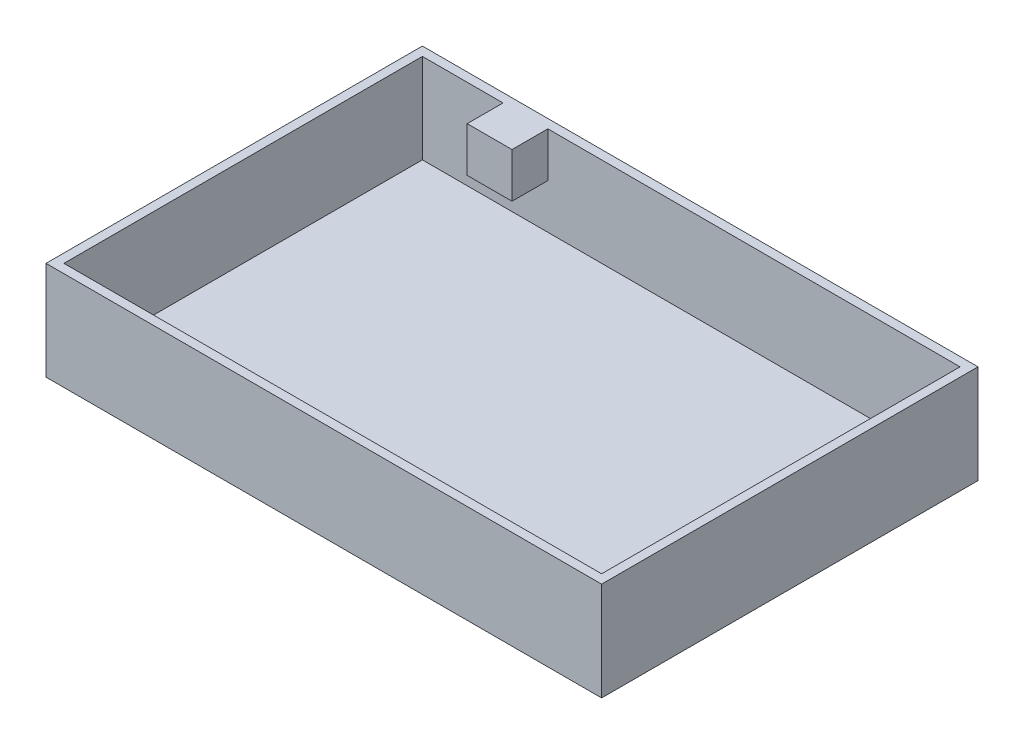
SolidWorks part; units mm, degrees
ref_plane "Front Plane" through (0, 0, 0) normal (0, 0, 1) x (1, 0, 0)
ref_plane "Top Plane" through (0, 0, 0) normal (0, 1, 0) x (1, 0, 0)
ref_plane "Right Plane" through (0, 0, 0) normal (1, 0, 0) x (0, 0, -1)
sketch "Sketch1" plane through (0, 0, 0) normal (0, 1, 0) x (1, 0, 0)
  line L1 (-60, 40) -> (60, 40)
  line L2 (-60, 40) -> (-60, -40)
  line L3 (-60, -40) -> (60, -40)
  line L4 (60, 40) -> (60, -40)
  line L5 (-60, 40) -> (60, -40) construction
  line L6 (-60, -40) -> (60, 40) construction
  point P0 (0, 0)
  dimension "D1" = 120
  dimension "D2" = 80
extrude "Extrude-Thin1" add sketch "Sketch1" along normal blind 20 thin thin type one direction wall 2
sketch "Sketch2" plane through (0, 0, 0) normal (0, -1, 0) x (1, 0, 0)
  line L4 (62, -42) -> (62, 42)
  line L5 (62, 42) -> (-62, 42)
  line L6 (-62, 42) -> (-62, -42)
  line L7 (-62, -42) -> (62, -42)
  line L8 (62, -42) -> (62, 42)
  line L9 (62, 42) -> (-62, 42)
  line L10 (-62, 42) -> (-62, -42)
  line L11 (-62, -42) -> (62, -42)
  dimension "D1" = 0
extrude "Boss-Extrude1" add sketch "Sketch2" along normal blind 2 contours L8 L9 L10 L11
sketch "Sketch3" plane through (0, 0, -40) normal (0, 0, 1) x (1, 0, 0)
  line L0 (62, 20) -> (-62, 20) construction
  line L1 (-32, 20) -> (-42, 20)
  line L2 (-32, 20) -> (-32, 10)
  line L3 (-32, 10) -> (-42, 10)
  line L4 (-42, 20) -> (-42, 10)
  line L5 (-62, 20) -> (-62, -2) construction
  dimension "D1" = 10
  dimension "D2" = 10
  dimension "D3" = 20
extrude "Boss-Extrude2" add sketch "Sketch3" along normal blind 8
sketch "Sketch4" plane through (0, 0, -32) normal (0, 0, 1) x (1, 0, 0)
  line L0 (-32, 20) -> (-35.3519, 20)
  line L1 (62, 20) -> (-62, 20) construction
  line L2 (-35.3519, 20) -> (-35.3519, 14.4216)
  line L3 (-35.3519, 14.4216) -> (-42, 20)
  line L4 (-42, 10) -> (-32, 10) construction
  line L9 (-32, 10) -> (-32, 20)
  line L10 (-32, 20) -> (-42, 20)
  line L11 (-42, 20) -> (-42, 10)
  line L12 (-42, 10) -> (-32, 10)
  line L13 (-32, 10) -> (-32, 20)
  line L14 (-32, 20) -> (-35.3519, 20)
  line L15 (-42, 20) -> (-42, 10)
  line L16 (-42, 10) -> (-32, 10)
  dimension "D1" = 40
  dimension "D2" = 0
